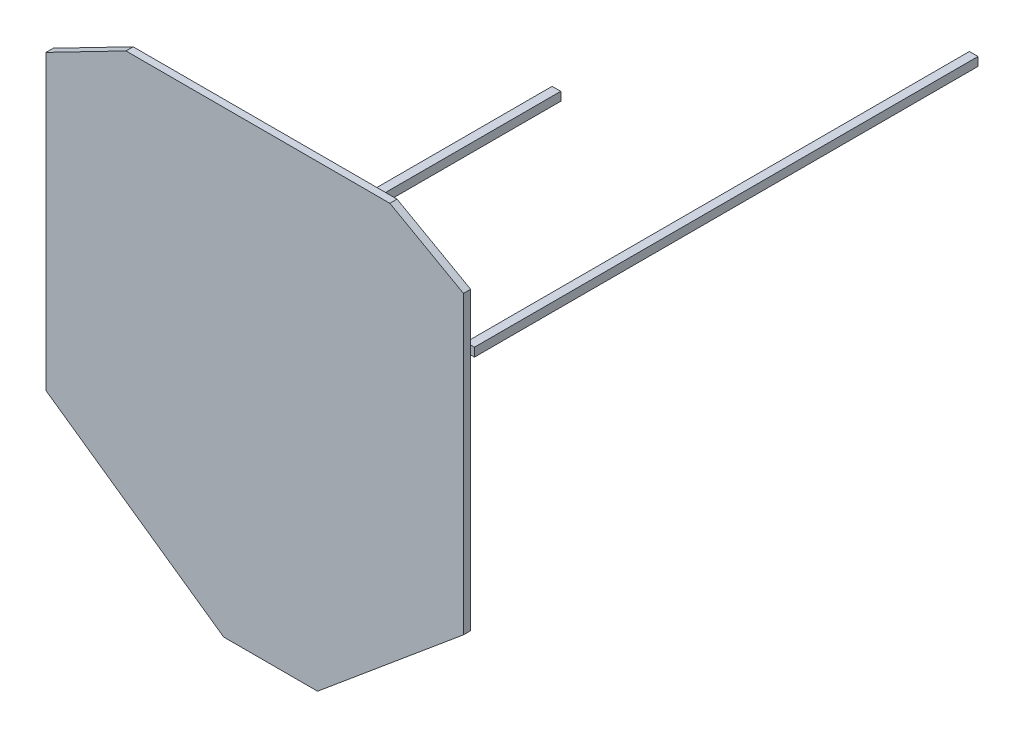
SolidWorks part; units mm, degrees
ref_plane "Front" through (0, 0, 0) normal (0, 0, 1) x (1, 0, 0)
ref_plane "Top" through (0, 0, 0) normal (0, 1, 0) x (1, 0, 0)
ref_plane "Right" through (0, 0, 0) normal (1, 0, 0) x (0, 0, -1)
sketch "Esquisse1" plane through (0, 0, 0) normal (0, 0, 1) x (1, 0, 0)
  line L1 (0, 0) -> (50, 0)
  line L2 (0, 0) -> (0, 50)
  line L3 (0, 50) -> (50, 50)
  line L4 (50, 0) -> (50, 50)
  dimension "D1" = 50
  dimension "D2" = 50
extrude "Boss.-Extru.1" add sketch "Esquisse1" along normal blind 5
sketch "Esquisse2" plane through (0, 0, 5) normal (0, 0, 1) x (1, 0, 0)
  line L0 (-2.7685, 83.8148) -> (52.7948, 112.4784)
  line L1 (52.7948, 112.4784) -> (236.2421, 112.4784)
  line L2 (236.2421, 112.4784) -> (287.3728, 83.8148)
  line L3 (287.3728, 83.8148) -> (287.3728, -121.7217)
  line L4 (287.3728, -121.7217) -> (185.9705, -206.3494)
  line L5 (185.9705, -206.3494) -> (120.7056, -206.3494)
  line L6 (120.7056, -206.3494) -> (-2.7685, -119.7806)
  line L7 (-2.7685, -119.7806) -> (-2.7685, 83.8148)
  point P5 (185.9705, -206.3494)
  point P10 (120.7056, -206.3494)
  point P11 (287.3728, 83.8148)
  point P12 (236.2421, 112.4784)
  point P13 (0, 0)
  point P14 (-2.7685, 83.8148)
  point P15 (52.7948, 112.4784)
extrude "Boss.-Extru.2" add sketch "Esquisse2" against normal up to vertex (5 mm away) up to point (0, 50, 0)
sketch "Esquisse3" plane through (0, 0, 0) normal (0, 0, -1) x (-1, 0, 0)
  line L0 (0, -121.7217) -> (6, -121.7217)
  line L1 (6, -121.7217) -> (6, -115.7217)
  line L2 (6, -115.7217) -> (0, -115.7217)
  line L4 (0, -115.7217) -> (0, -121.7217)
  line L6 (-284, 44.2389) -> (-290, 44.2389)
  line L7 (-284, 44.2389) -> (-284, 50.2389)
  line L8 (-284, 50.2389) -> (-290, 50.2389)
  line L9 (-290, 44.2389) -> (-290, 50.2389)
  point P6 (0, 0)
  point P7 (0, 0)
  point P11 (0, 0)
  dimension "D1" = 6
  dimension "D2" = 6
  dimension "D3" = 6
  dimension "D4" = 6
extrude "Boss.-Extru.3" add sketch "Esquisse3" along normal blind 350
